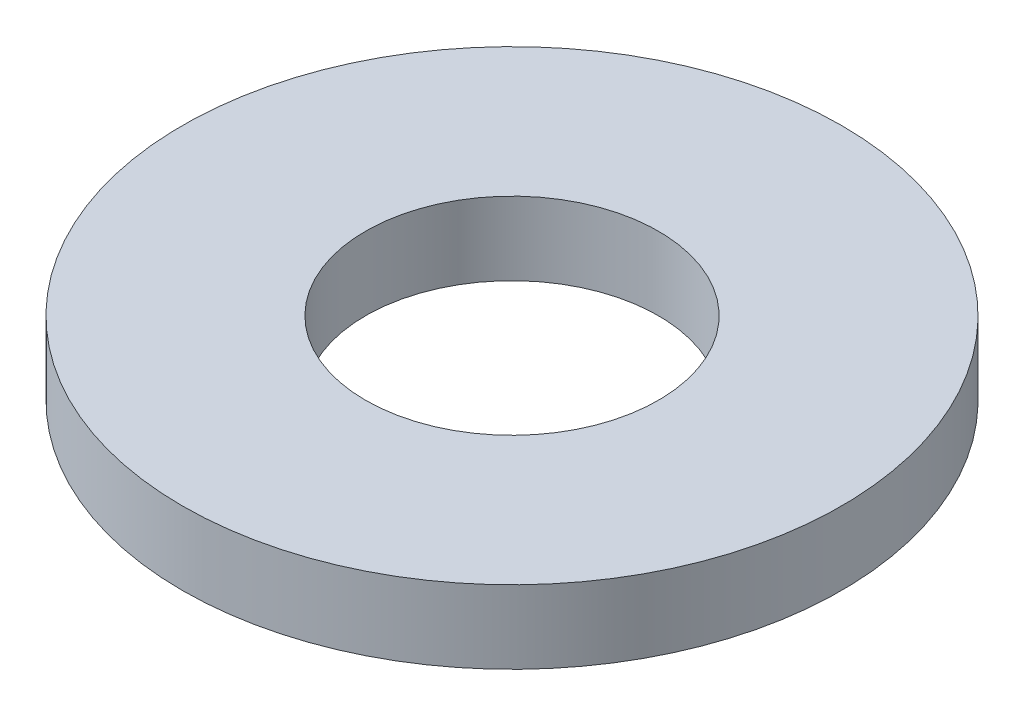
SolidWorks part; units mm, degrees
ref_plane "Front Plane" through (0, 0, 0) normal (0, 0, 1) x (1, 0, 0)
ref_plane "Top Plane" through (0, 0, 0) normal (0, 1, 0) x (1, 0, 0)
ref_plane "Right Plane" through (0, 0, 0) normal (1, 0, 0) x (0, 0, -1)
sketch "Sketch1" plane through (0, 0, 0) normal (0, 1, 0) x (1, 0, 0)
  circle A0 centre (0, 0) radius 67.5
  dimension "FLANGE_OD" = 135
extrude "Boss-Extrude1" add sketch "Sketch1" along normal blind 15
sketch "Sketch2" plane through (0, 0, 0) normal (0, 1, 0) x (1, 0, 0)
  circle A0 centre (0, 0) radius 30
  dimension "BORE_D" = 60
extrude "Cut-Extrude1" cut sketch "Sketch2" along normal through all
sketch "Sketch3" plane through (0, 15, 0) normal (0, 1, 0) x (1, 0, 0)
  circle A0 centre (0, 0) radius 25.9118 construction
  circle A1 centre (-25.9118, 0) radius 3.7653
  dimension "BOLT_D" = 7.5307
  dimension "BOLT_PCD" = 51.8236
extrude "Cut-Extrude2" cut sketch "Sketch3" against normal blind 11.7761 rebuild error yes
pattern_circular "CirPattern1" count 8 over 360 rebuild error yes
